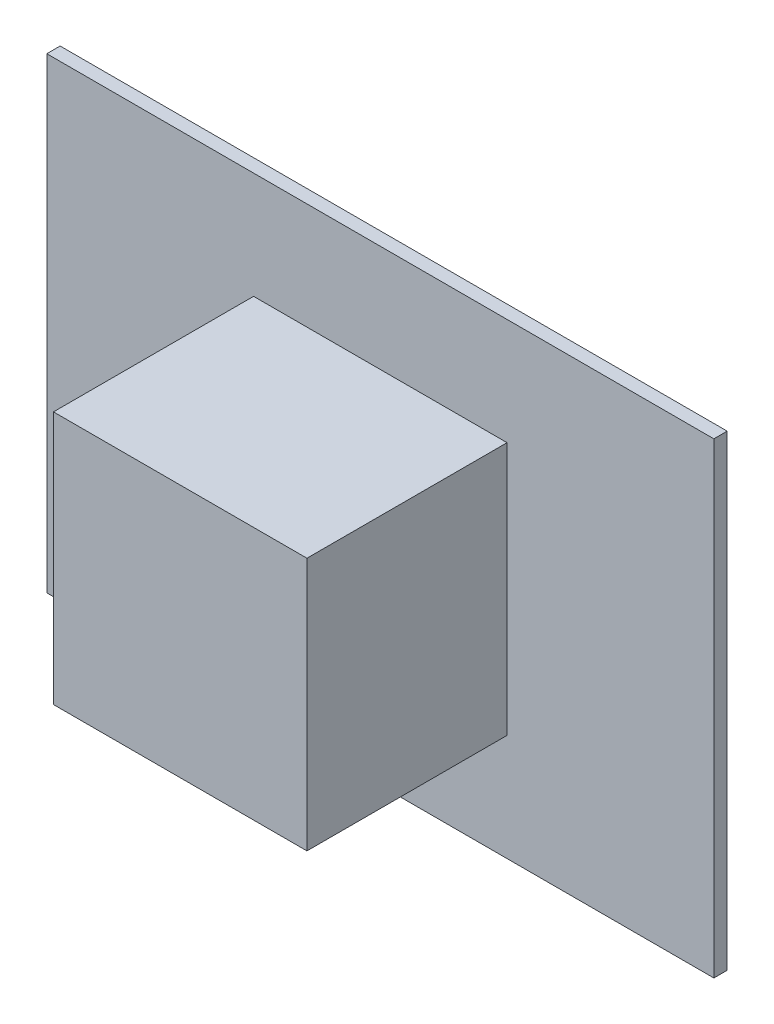
SolidWorks part; units mm, degrees
ref_plane "Front Plane" through (0, 0, 0) normal (0, 0, 1) x (1, 0, 0)
ref_plane "Top Plane" through (0, 0, 0) normal (0, 1, 0) x (1, 0, 0)
ref_plane "Right Plane" through (0, 0, 0) normal (1, 0, 0) x (0, 0, -1)
sketch "Sketch1" plane through (0, 0, 0) normal (0, 0, 1) x (1, 0, 0)
  line L1 (0.95, -0.95) -> (-0.95, -0.95)
  line L2 (0.95, -0.95) -> (0.95, 0.95)
  line L3 (0.95, 0.95) -> (-0.95, 0.95)
  line L4 (-0.95, -0.95) -> (-0.95, 0.95)
  line L5 (0.95, -0.95) -> (-0.95, 0.95) construction
  line L6 (0.95, 0.95) -> (-0.95, -0.95) construction
  point P0 (0, 0)
  dimension "D1" = 1.9
  dimension "D2" = 1.9
extrude "Boss-Extrude1" add sketch "Sketch1" along normal blind 2
sketch "Sketch3" plane through (0, 0, 0) normal (1, 0, 0) x (0, 0, -1)
  line L0 (0, 0) -> (0, 0.7)
  line L1 (0, -0.95) -> (0, 0.95) construction
  line L2 (0, 0.7) -> (-0.9722, 0.7)
  line L3 (0, 0) -> (-1.6629, 0)
  arc A0 (-1.6629, 0) -> (-0.9722, 0.7) centre (-0.9629, 0) cw
  dimension "D1" = 0.7
ref_axis "Axis1" through (0, 0, 5.25) along (0, 0, -1)
revolve "Cut-Revolve1" cut sketch "Sketch3" angle 360 about axis through (0, 0, 5.25) along (0, 0, -1)
ref_plane "Plane1" through (0, 0, 0.4) normal (0, 0, 1) x (1, 0, 0)
sketch "Sketch4" plane through (0, 0, 0.4) normal (0, 0, 1) x (1, 0, 0)
  line L1 (-2.5, 1.75) -> (2.5, 1.75)
  line L2 (-2.5, 1.75) -> (-2.5, -1.75)
  line L3 (-2.5, -1.75) -> (2.5, -1.75)
  line L4 (2.5, 1.75) -> (2.5, -1.75)
  line L5 (-2.5, 1.75) -> (2.5, -1.75) construction
  line L6 (-2.5, -1.75) -> (2.5, 1.75) construction
  line L7 (0.765, 0.7369) -> (-0.765, 0.7369)
  line L8 (0.765, 0.7369) -> (0.765, -0.7369)
  line L9 (0.765, -0.7369) -> (-0.765, -0.7369)
  line L10 (-0.765, 0.7369) -> (-0.765, -0.7369)
  line L11 (0.765, 0.7369) -> (-0.765, -0.7369) construction
  line L12 (0.765, -0.7369) -> (-0.765, 0.7369) construction
  point P0 (0, 0)
  point P6 (0, 0)
  dimension "D1" = 5
  dimension "D2" = 3.5
extrude "Boss-Extrude2" add sketch "Sketch4" along normal blind 0.1
